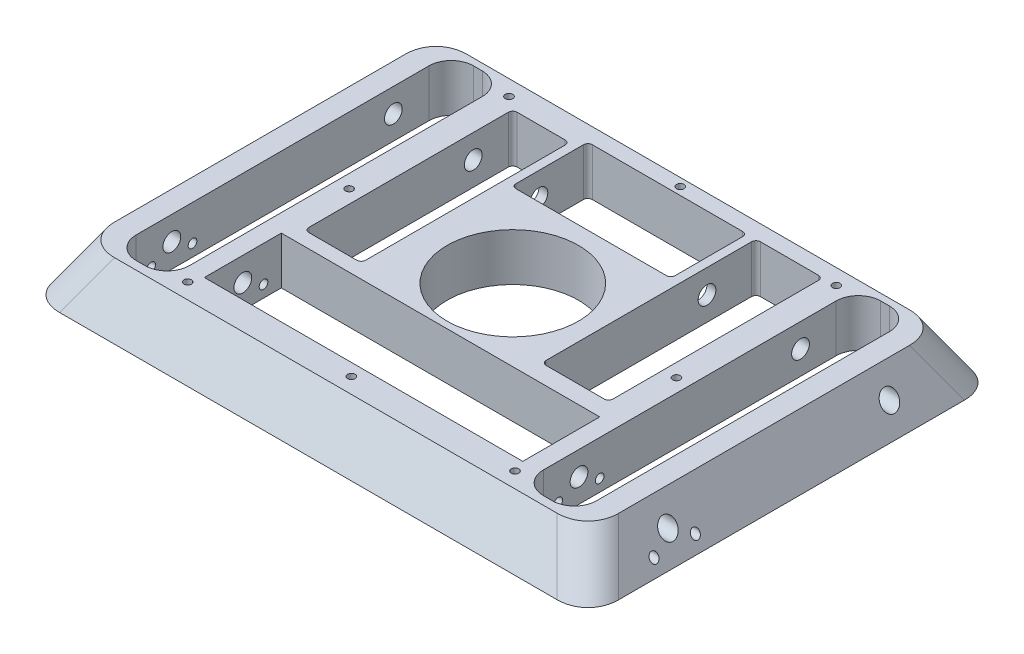
SolidWorks part; units mm, degrees
material "PE High Density"
ref_plane "Front Plane" through (0, 0, 0) normal (0, 0, 1) x (1, 0, 0)
ref_plane "Top Plane" through (0, 0, 0) normal (0, 1, 0) x (1, 0, 0)
ref_plane "Right Plane" through (0, 0, 0) normal (1, 0, 0) x (0, 0, -1)
sketch "Sketch1" plane through (0, 0, 0) normal (0, 1, 0) x (1, 0, 0)
  line L0 (-74.422, 60.325) -> (-71.247, 60.325)
  line L1 (-100.0125, 77.978) -> (100.0125, 77.978)
  line L2 (-100.0125, 77.978) -> (-100.0125, -77.978)
  line L3 (-100.0125, -77.978) -> (100.0125, -77.978)
  line L4 (100.0125, 77.978) -> (100.0125, -77.978)
  line L5 (-100.0125, 77.978) -> (100.0125, -77.978) construction
  line L6 (-100.0125, -77.978) -> (100.0125, 77.978) construction
  line L7 (0, 76.195) -> (0, -94.2073) construction
  line L8 (-74.422, -60.325) -> (-71.247, -60.325)
  line L9 (-82.3595, 52.3875) -> (-82.3595, -52.3875)
  line L10 (-63.3095, 52.3875) -> (-63.3095, -52.3875)
  line L11 (-82.3595, -60.325) -> (82.3595, -60.325) construction
  line L12 (-82.3595, 60.325) -> (-82.3595, -60.325) construction
  line L13 (-82.3595, 60.325) -> (82.3595, 60.325) construction
  line L14 (82.3595, 60.325) -> (82.3595, -60.325) construction
  line L15 (74.422, -60.325) -> (71.247, -60.325)
  line L16 (82.3595, 52.3875) -> (82.3595, -52.3875)
  line L17 (63.3095, 52.3875) -> (63.3095, -52.3875)
  line L18 (74.422, 60.325) -> (71.247, 60.325)
  line L19 (-52.197, 60.325) -> (52.197, 60.325) construction
  line L20 (56.9595, 55.5625) -> (56.9595, -55.5625) construction
  line L21 (52.197, -60.325) -> (-52.197, -60.325) construction
  line L22 (-56.9595, -55.5625) -> (-56.9595, 55.5625) construction
  line L23 (-111.9568, -39.624) -> (100.2292, -39.624) construction
  line L24 (-56.9595, -52.124) -> (-1.9595, -52.124) construction
  line L25 (-56.9595, -52.124) -> (-56.9595, -27.124) construction
  line L26 (-56.9595, -27.124) -> (-1.9595, -27.124) construction
  line L27 (-1.9595, -52.124) -> (-1.9595, -27.124) construction
  line L28 (1.9595, -52.124) -> (1.9595, -27.124) construction
  line L29 (56.9595, -52.124) -> (1.9595, -52.124) construction
  line L30 (56.9595, -27.124) -> (1.9595, -27.124) construction
  line L31 (-139.1352, 0) -> (137.9452, 0) construction
  line L32 (-111.9568, 39.624) -> (100.2292, 39.624) construction
  line L33 (-56.9595, -53.394) -> (56.9595, -53.394)
  line L34 (-52.5145, -19.504) -> (-34.7345, -19.504) construction
  line L35 (-52.5145, -19.504) -> (-52.5145, 52.496) construction
  line L36 (-52.5145, 52.496) -> (-34.7345, 52.496) construction
  line L37 (-34.7345, -19.504) -> (-34.7345, 52.496) construction
  line L38 (-56.9595, -53.394) -> (-1.9595, -53.394) construction
  line L39 (-56.9595, -25.854) -> (56.9595, -25.854)
  line L40 (-56.9595, -25.854) -> (-1.9595, -25.854) construction
  line L41 (-53.7845, -19.1865) -> (-53.7845, 52.1785)
  line L42 (-52.197, 53.766) -> (-35.052, 53.766)
  line L43 (-33.4645, -19.1865) -> (-33.4645, 52.1785)
  line L44 (-52.197, -20.774) -> (-35.052, -20.774)
  line L45 (-56.9595, -25.854) -> (-56.9595, -53.394)
  line L46 (52.197, -19.504) -> (31.4325, -19.504)
  line L47 (53.7845, -17.9165) -> (53.7845, 55.5625)
  line L48 (52.197, 57.15) -> (31.4325, 57.15)
  line L49 (29.845, -17.9165) -> (29.845, 55.5625)
  line L50 (25.0825, 57.15) -> (-28.702, 57.15)
  line L51 (26.67, 55.5625) -> (26.67, 31.4325)
  line L52 (25.0825, 29.845) -> (-28.702, 29.845)
  line L53 (-30.2895, 55.5625) -> (-30.2895, 31.4325)
  line L54 (56.9595, -53.394) -> (56.9595, -25.854)
  line L55 (-33.4645, -20.774) -> (-33.4645, 53.766) construction
  line L56 (-53.7845, 53.766) -> (-33.4645, 53.766) construction
  line L57 (-53.7845, -20.774) -> (-33.4645, -20.774) construction
  line L58 (-53.7845, -20.774) -> (-53.7845, 53.766) construction
  circle A0 centre (0, 0) radius 25.019 construction
  arc A1 (-71.247, -60.325) -> (-63.3095, -52.3875) centre (-71.247, -52.3875) ccw
  arc A2 (-74.422, -60.325) -> (-82.3595, -52.3875) centre (-74.422, -52.3875) cw
  arc A3 (-74.422, 60.325) -> (-82.3595, 52.3875) centre (-74.422, 52.3875) ccw
  arc A4 (-63.3095, 52.3875) -> (-71.247, 60.325) centre (-71.247, 52.3875) ccw
  arc A5 (71.247, -60.325) -> (63.3095, -52.3875) centre (71.247, -52.3875) cw
  arc A6 (74.422, -60.325) -> (82.3595, -52.3875) centre (74.422, -52.3875) ccw
  arc A7 (63.3095, 52.3875) -> (71.247, 60.325) centre (71.247, 52.3875) cw
  arc A8 (74.422, 60.325) -> (82.3595, 52.3875) centre (74.422, 52.3875) cw
  arc A9 (52.197, -60.325) -> (56.9595, -55.5625) centre (52.197, -55.5625) ccw construction
  arc A10 (-56.9595, -55.5625) -> (-52.197, -60.325) centre (-52.197, -55.5625) ccw construction
  arc A11 (52.197, 60.325) -> (56.9595, 55.5625) centre (52.197, 55.5625) cw construction
  arc A12 (-52.197, 60.325) -> (-56.9595, 55.5625) centre (-52.197, 55.5625) ccw construction
  circle A13 centre (0, 0) radius 23.495
  circle A14 centre (0, 0) radius 29.845 construction
  arc A15 (52.197, 57.15) -> (53.7845, 55.5625) centre (52.197, 55.5625) cw
  arc A16 (53.7845, -17.9165) -> (52.197, -19.504) centre (52.197, -17.9165) cw
  arc A17 (31.4325, -19.504) -> (29.845, -17.9165) centre (31.4325, -17.9165) cw
  arc A18 (-30.2895, 31.4325) -> (-28.702, 29.845) centre (-28.702, 31.4325) ccw
  arc A19 (31.4325, 57.15) -> (29.845, 55.5625) centre (31.4325, 55.5625) ccw
  arc A20 (26.67, 55.5625) -> (25.0825, 57.15) centre (25.0825, 55.5625) ccw
  arc A21 (26.67, 31.4325) -> (25.0825, 29.845) centre (25.0825, 31.4325) cw
  arc A22 (-30.2895, 55.5625) -> (-28.702, 57.15) centre (-28.702, 55.5625) cw
  arc A23 (-33.4645, 52.1785) -> (-35.052, 53.766) centre (-35.052, 52.1785) ccw
  arc A24 (-35.052, -20.774) -> (-33.4645, -19.1865) centre (-35.052, -19.1865) ccw
  arc A25 (-53.7845, -19.1865) -> (-52.197, -20.774) centre (-52.197, -19.1865) ccw
  arc A26 (-53.7845, 52.1785) -> (-52.197, 53.766) centre (-52.197, 52.1785) cw
  point P0 (0, 0)
  point P57 (-1.9595, -39.624)
  dimension "D3" = 50.038
  dimension "D1" = 7.9375
  dimension "D8" = 4.7625
  dimension "D9" = 46.99
  dimension "D27" = 1.5875
  dimension "D2" = 120.65
  dimension "D5" = 19.05
  dimension "D6" = 6.35
  dimension "D7" = 6.35
  dimension "D10" = 200.025
  dimension "D11" = 55
  dimension "D12" = 25
  dimension "D13" = 20.701
  dimension "D14" = 17.78
  dimension "D15" = 72
  dimension "D16" = 1.27
  dimension "D19" = 6.35
  dimension "D20" = 1.27
  dimension "D21" = 3.175
  dimension "D22" = 3.175
  dimension "D23" = 3.175
  dimension "D24" = 6.35
  dimension "D25" = 3.175
  dimension "D26" = 3.175
  dimension "D4" = 17.653
  dimension "D17" = 6.35
  dimension "D18" = 1.27
extrude "Boss-Extrude1" add sketch "Sketch1" along normal blind 17 contours L4 L1 L2 L3 A12 L19 A11 L20 A9 L21 A10 L22 A4 L10 A1 L8 A2 L9 A3 L0 L18 A8 L16 A6 L15 A5 L17 A7 | L19 A12 L22 L39 L20 A11 A13 L44 L41 L42 L43
sketch "Sketch2" plane through (-100.0125, 0, 0) normal (-1, 0, 0) x (0, 0, 1)
  line L0 (77.978, 17) -> (77.978, 0) construction
  line L1 (-77.978, 17) -> (-77.978, 0) construction
  line L2 (-77.978, 17) -> (77.978, 17) construction
  circle A0 centre (39.624, 8.491) radius 3.175
  circle A1 centre (-39.624, 8.491) radius 3.175
  dimension "D1" = 6.35
  dimension "D3" = 38.354
  dimension "D4" = 6.35
  dimension "D2" = 38.354
  dimension "D5" = 8.509
  dimension "D6" = 8.509
extrude "Cut-Extrude1" cut sketch "Sketch2" against normal through all
sketch "Sketch3" plane through (-100.0125, 0, 0) normal (-1, 0, 0) x (0, 0, 1)
  line L0 (-77.978, 17) -> (77.978, 17) construction
  circle A0 centre (47.019, 4.3) radius 1.55
  circle A1 centre (32.229, 4.3) radius 1.55
  circle A2 centre (39.624, 8.491) radius 3.175 construction
  dimension "D1" = 8.5
  dimension "D2" = 8.5
  dimension "D3" = 3.1
  dimension "D4" = 3.1
  dimension "D5" = 12.7
  dimension "D6" = 12.7
extrude "Cut-Extrude2" cut sketch "Sketch3" against normal through all
chamfer "Chamfer1" distance 25.4 angle 30 2 edges at (0, 0, 77.978) (0, 17, 77.978)
chamfer "Chamfer2" distance 15.24 angle 60 2 edges at (0, 0, -77.978) (0, 17, -77.978)
sketch "Sketch5" plane through (0, 0, 0) normal (0, 0, 1) x (1, 0, 0)
  line L0 (100.0125, 0) -> (90.1975, 17)
  line L1 (100.0125, 17) -> (-100.0125, 17) construction
  line L2 (-100.0125, 0) -> (100.0125, 0) construction
  line L5 (100.0125, 0) -> (100.0125, 17)
  line L6 (100.0125, 17) -> (90.1975, 17)
  dimension "D1" = 60
extrude "Cut-Extrude5" cut sketch "Sketch5" against normal through all and the other way through all
mirror "Mirror1" about plane through (0, 0, 0) normal (1, 0, 0) of "Cut-Extrude5"
fillet "Fillet1" radius 12.7 4 edges at (-95.105, 8.5, 68.2208) (-95.105, 8.5, -67.6455) (95.105, 8.5, 68.2208) (95.105, 8.5, -67.6455)
hole_wizard "Tap Drill for #6-32 Tap1" positions "Sketch7" profile "Sketch6" hole size "#6-32" standard "ANSI Inch" end condition through all
sketch "Sketch7" plane through (0, 17, 0) normal (0, 1, 0) x (1, 0, 0)
  line L0 (-63.3095, 0) -> (-53.7845, 0) construction
  line L1 (-63.3095, 52.3875) -> (-63.3095, -52.3875) construction
  line L2 (-53.7845, -19.1865) -> (-53.7845, 52.1785) construction
  line L4 (53.7845, 0) -> (63.3095, 0) construction
  line L5 (53.7845, -17.9165) -> (53.7845, 55.5625) construction
  line L6 (63.3095, 52.3875) -> (63.3095, -52.3875) construction
  line L8 (-58.547, -46.9259) -> (-58.547, 36.9417) construction
  line L12 (79.199, 62.738) -> (-79.199, 62.738) construction
  line L13 (-79.199, -63.3133) -> (79.199, -63.3133) construction
  line L14 (0, 83.7048) -> (0, -84.2801) construction
  point P0 (-58.547, 57.1817)
  point P2 (-58.547, 0)
  point P38 (-58.547, -57.7571)
  point P50 (58.547, -57.7571)
  point P51 (58.547, 0)
  point P52 (58.547, 57.1817)
  point P55 (0, 59.9069)
  point P58 (0, -57.7571)
  dimension "D1" = 5.5562
  dimension "D2" = 5.5562
sketch "Sketch6" plane through (-58.547, 17, -57.1817) normal (1, 0, 0) x (0, 0, 1)
  line L0 (0, 0) -> (0, 17)
  line L1 (0, 17) -> (1.3525, 17)
  line L2 (1.3525, 17) -> (1.3525, 0)
  line L5 (1.3525, 0) -> (0, 0)
  line L11 (0, -6.35) -> (0, 107.95) construction
  dimension "Thru Hole Dia." = 2.7051
  dimension "Thru Hole Depth" = 17
hole_wizard "Tap Drill for #6-32 Tap2" [suppressed] positions "Sketch10" profile "Sketch9" hole size "#6-32" standard "ANSI Inch"
sketch "Sketch10" [suppressed] plane through (0, 33.5164, -58.052) normal (0, 0.5, -0.866) x (-1, 0, 0)
  line L0 (0, -9.372) -> (0, -38.7013) construction
  line L1 (-74.3493, -9.372) -> (74.3493, -9.372) construction
  line L2 (89.014, -38.7013) -> (-89.014, -38.7013) construction
  line L4 (-74.3493, -9.372) -> (-89.014, -38.7013) construction
  point P0 (-70.4248, -15.722)
  point P2 (-78.7395, -32.3513)
  point P13 (70.4248, -15.722)
  point P14 (78.7395, -32.3513)
  dimension "D1" = 6.35
  dimension "D2" = 6.35
  dimension "D3" = 6.35
  dimension "D4" = 6.35
sketch "Sketch9" plane through (70.4248, 19.9007, -65.913) normal (1, 0, 0) x (0, 0.866, 0.5)
  line L0 (0, 0) -> (0, 26.2127)
  line L1 (0, 26.2127) -> (1.3525, 25.4)
  line L2 (1.3525, 25.4) -> (1.3525, 0)
  line L5 (1.3525, 0) -> (0, 0)
  line L10 (0, 26.2127) -> (-1.3526, 25.4) construction
  line L11 (0, -6.35) -> (0, 107.95) construction
  dimension "Hole Dia." = 2.7051
  dimension "Hole Depth" = 25.4
  dimension "Drill Angle" = 118
equation "\"D3@Sketch2\"=\"D2@Sketch2\""
equation "\"D4@Sketch2\"=\"D1@Sketch2\""
equation "\"D6@Sketch2\"=\"Height\"/2"
equation "\"Height\"= .67"
equation "\"D5@Sketch2\"=\"Height\"/2"
